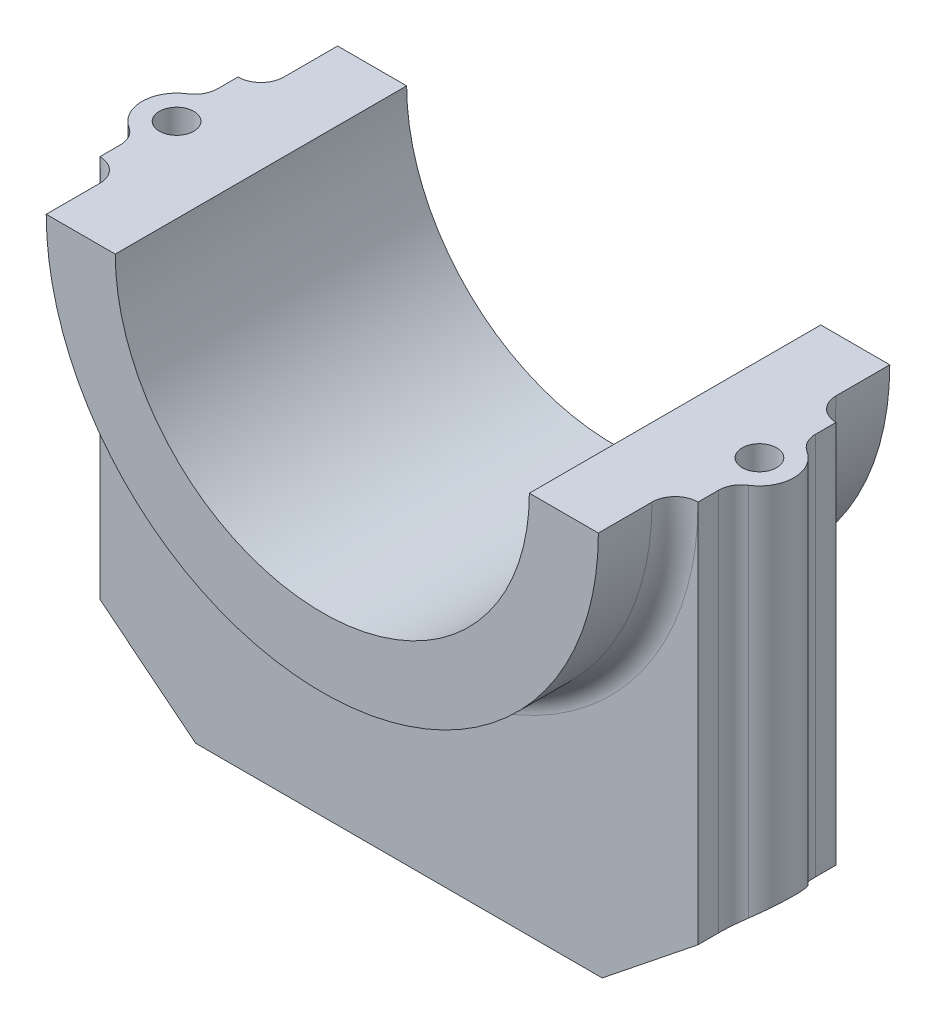
SolidWorks part; units mm, degrees
material "7075-T6, Plate (SS)"
ref_plane "Front Plane" through (0, 0, 0) normal (0, 0, 1) x (1, 0, 0)
ref_plane "Top Plane" through (0, 0, 0) normal (0, 1, 0) x (1, 0, 0)
ref_plane "Right Plane" through (0, 0, 0) normal (1, 0, 0) x (0, 0, -1)
sketch "Sketch1" plane through (0, 0, 0) normal (0, 0, 1) x (1, 0, 0)
  line L0 (-27, 0) -> (-39, 0)
  line L1 (-39, 0) -> (-39, -50)
  line L2 (-39, -50) -> (-26.5, -60)
  line L3 (-26.5, -60) -> (26.5, -60)
  line L4 (26.5, -60) -> (39, -50)
  line L5 (39, -50) -> (39, 0)
  line L6 (39, 0) -> (27, 0)
  line L7 (-39, -50) -> (-51.5, -40)
  line L8 (-51.5, -40) -> (-51.5, 0)
  line L9 (-51.5, 0) -> (-39, 0)
  line L10 (0, 0) -> (0, 50000) construction
  line L11 (39, -50) -> (51.5, -40)
  line L12 (51.5, 0) -> (39, 0)
  line L13 (51.5, -40) -> (51.5, 0)
  arc A0 (27, 0) -> (-27, 0) centre (0, 0) cw
  arc A1 (36, 0) -> (-36, 0) centre (0, 0) cw
  dimension "D1" = 27
  dimension "D2" = 36
  dimension "D3" = 60
  dimension "D4" = 25
  dimension "D5" = 3
  dimension "D6" = 20
extrude "Boss-Extrude1" add sketch "Sketch1" along normal mid plane 38 contours A1 L10 A0 L0 | L10 A1 L6 A0 region at (0, -27.805, 0)
extrude "Boss-Extrude2" add sketch "Sketch1<3>" along normal mid plane 18 contours L10 L3 L4 L5 L6 A1 | L3 L10 A1 L0 L1 L2 | L9 L8 L7 L1 | L11 L13 L12 L5 region at (0, -40.5727, 0) region at (-45.0185, -22.5926, 0) region at (45.0185, -22.5926, 0)
sketch "Sketch1<3>" plane through (0, 0, 0) normal (0, 0, 1) x (1, 0, 0) same geometry as "Sketch1"
sketch "Sketch2" plane through (0, 0, 0) normal (0, 1, 0) x (1, 0, 0)
  line L0 (0, -20.9) -> (0, 20.9) construction
  line L1 (36, 9) -> (36, 4.0311)
  line L2 (51.5, -9) -> (36, -9) construction
  line L3 (36, -4.0311) -> (36, -9)
  line L4 (36, 9) -> (51.5, 9)
  line L5 (51.5, 9) -> (51.5, -9)
  line L6 (51.5, -9) -> (36, -9)
  line L7 (-36, 9) -> (-36, 4.0311)
  line L8 (-36, -9) -> (-51.5, -9)
  line L9 (-51.5, -9) -> (-51.5, 9)
  line L10 (-51.5, 9) -> (-36, 9)
  line L11 (-36, -4.0311) -> (-36, -9)
  line L12 (-39, 9) -> (-39, -9)
  line L13 (39, 9) -> (39, -9)
  arc A0 (36, -4.0311) -> (36, 4.0311) centre (38, 0) ccw
  arc A1 (-36, -4.0311) -> (-36, 4.0311) centre (-38, 0) cw
  circle A2 centre (-38, 0) radius 2.25
  circle A3 centre (38, 0) radius 2.25
  point P32 (-36, -6.5156)
  dimension "D1" = 9
  dimension "D3" = 4.5
  dimension "D2" = 76
  dimension "D4" = 3
fillet "Fillet5" radius 3 2 edges at (0, -36, -9) (0, -36, 9)
extrude "Cut-Extrude2" cut sketch "Sketch2" against normal up to next contours L12 A1 L10 L9 L8 | A0 L13 L6 L5 L4 | A3 L13 | L12 A2 | L12 A2 | A3 L13 region at (45.7922, 0, 0) region at (39.5142, 0, 0) region at (37.5562, 0, 0) region at (-45.7922, 0, 0) region at (-37.5562, 0, 0) region at (-39.5142, 0, 0)
fillet "Fillet6" radius 3 4 edges at (-39, -25, -4.3875) (-39, -25, 4.3875) (39, -25, 4.3875) (39, -25, -4.3875)
